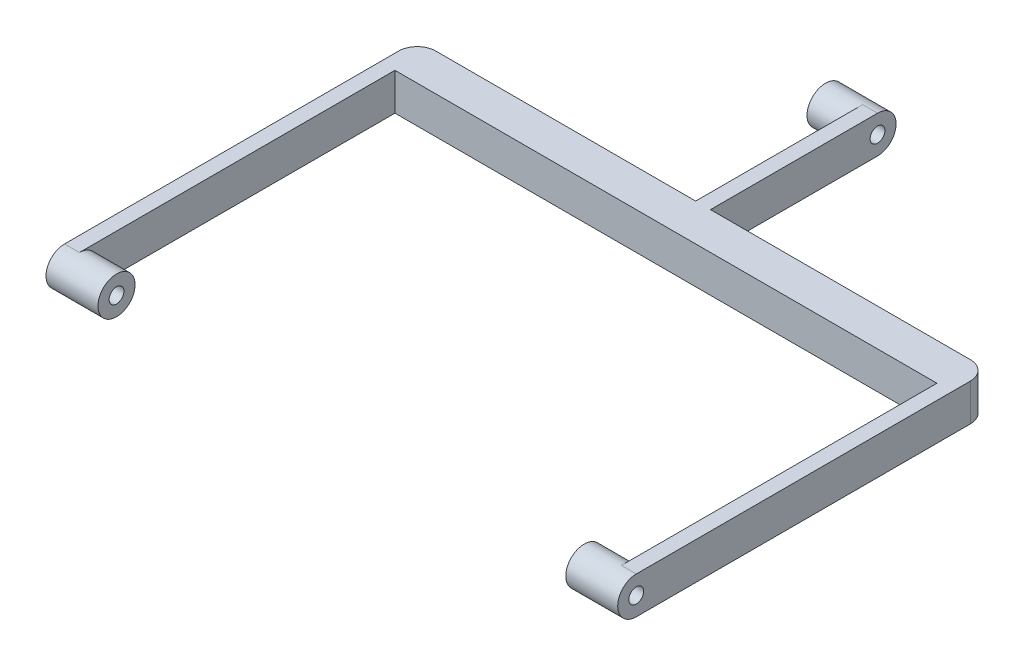
SolidWorks part; units mm, degrees
ref_plane "Plano frontal" through (0, 0, 0) normal (0, 0, 1) x (1, 0, 0)
ref_plane "Plano superior" through (0, 0, 0) normal (0, 1, 0) x (1, 0, 0)
ref_plane "Plano direito" through (0, 0, 0) normal (1, 0, 0) x (0, 0, -1)
sketch "Esboço1" plane through (0, 0, 0) normal (0, 1, 0) x (1, 0, 0)
  line L1 (-38.5, -2.5) -> (38.5, -2.5)
  line L2 (-38.5, -2.5) -> (-38.5, 2.5)
  line L3 (-38.5, 2.5) -> (38.5, 2.5)
  line L4 (38.5, -2.5) -> (38.5, 2.5)
  line L5 (-38.5, -2.5) -> (38.5, 2.5) construction
  line L6 (-38.5, 2.5) -> (38.5, -2.5) construction
  point P0 (0, 0)
  dimension "D1" = 77
  dimension "D2" = 5
extrude "Ressalto-extrusão1" add sketch "Esboço1" along normal blind 5
sketch "Esboço2" plane through (0, 0, 0) normal (0, 1, 0) x (1, 0, 0)
  line L1 (-38.5, 2.5) -> (-36.5, 2.5)
  line L2 (-38.5, 2.5) -> (-38.5, -47.5)
  line L3 (-38.5, -47.5) -> (-36.5, -47.5)
  line L4 (-36.5, 2.5) -> (-36.5, -47.5)
  dimension "D1" = 2
  dimension "D2" = 50
extrude "Ressalto-extrusão2" add sketch "Esboço2" along normal blind 5
fillet "Filete1" radius 2.5 2 edges at (-37.5, 0, 47.5) (-37.5, 5, 47.5)
sketch "Esboço7" plane through (-36.5, 0, 0) normal (1, 0, 0) x (0, 0, -1)
  circle A0 centre (-45, 2.5) radius 2.5
  arc A1 (-45, 5) -> (-47.5, 2.5) centre (-45, 2.5) ccw construction
extrude "Ressalto-extrusão5" add sketch "Esboço7" along normal blind 5
sketch "Esboço3" plane through (0, 0, 0) normal (1, 0, 0) x (0, 0, -1)
  circle A0 centre (-45, 2.5) radius 1
  arc A1 (-45, 5) -> (-47.5, 2.5) centre (-45, 2.5) ccw construction
  dimension "D1" = 2
extrude "Corte-extrusão1" cut sketch "Esboço3" against normal through all
mirror "Espelhar1" about plane through (0, 0, 0) normal (1, 0, 0) of "Ressalto-extrusão5", "Corte-extrusão1", "Filete1", "Ressalto-extrusão2"
fillet "Filete2" radius 2.5 2 edges at (38.5, 2.5, -2.5) (-38.5, 2.5, -2.5)
sketch "Esboço4" plane through (0, 0, 0) normal (1, 0, 0) x (0, 0, -1)
  line L0 (-45, 5) -> (0, 5) construction
  line L1 (-2.5, 5) -> (27.5, 5)
  line L2 (-2.5, 5) -> (-2.5, 0)
  line L3 (-2.5, 0) -> (27.5, 0)
  line L4 (27.5, 5) -> (27.5, 0)
  line L5 (2.5, 5) -> (2.5, 0) construction
  dimension "D1" = 30
  dimension "D2" = 5
  dimension "D3" = 5
extrude "Ressalto-extrusão3" add sketch "Esboço4" along normal mid plane 2
fillet "Filete3" radius 2.5 2 edges at (0, 5, -27.5) (0, 0, -27.5)
sketch "Esboço6" plane through (-1, 0, 0) normal (-1, 0, 0) x (0, 0, 1)
  circle A0 centre (-25, 2.5) radius 2.5
  arc A1 (-27.5, 2.5) -> (-25, 0) centre (-25, 2.5) ccw construction
extrude "Ressalto-extrusão4" add sketch "Esboço6" along normal blind 5
sketch "Esboço5" plane through (0, 0, 0) normal (1, 0, 0) x (0, 0, -1)
  circle A0 centre (25, 2.5) radius 1
  arc A2 (27.5, 2.5) -> (25, 5) centre (25, 2.5) ccw construction
  dimension "D1" = 2
extrude "Corte-extrusão2" cut sketch "Esboço5" against normal through all both and the other way through all
